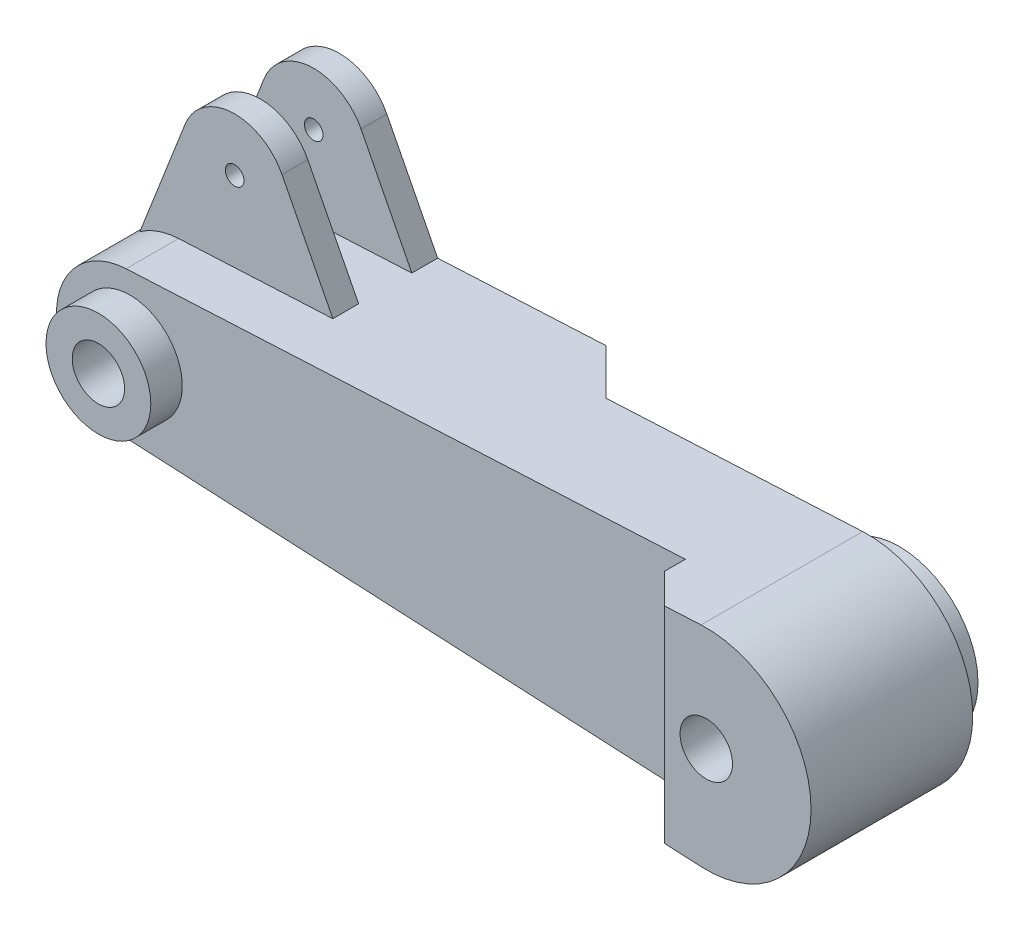
SolidWorks part; units mm, degrees
ref_plane "Front Plane" through (0, 0, 0) normal (0, 0, 1) x (1, 0, 0)
ref_plane "Top Plane" through (0, 0, 0) normal (0, 1, 0) x (1, 0, 0)
ref_plane "Right Plane" through (0, 0, 0) normal (1, 0, 0) x (0, 0, -1)
sketch "Sketch1" plane through (0, 0, 0) normal (0, 0, 1) x (1, 0, 0)
  line L0 (-60.35, 6.9912) -> (-0.5, 9.9875)
  line L1 (-60.35, -6.9912) -> (-0.5, -9.9875)
  arc A0 (-0.5, -9.9875) -> (-0.5, 9.9875) centre (0, 0) ccw
  arc A1 (-60.35, 6.9912) -> (-60.35, -6.9912) centre (-60, 0) ccw
  point P1 (0, 0)
  point P4 (-81.6059, 0)
  dimension "D1" = 7
  dimension "D2" = 10
  dimension "D3" = 60
extrude "Boss-Extrude1" add sketch "Sketch1" along normal blind 20
sketch "Sketch2" plane through (0, 0, 20) normal (0, 0, 1) x (1, 0, 0)
  circle A0 centre (-60, 0) radius 2.5
  arc A1 (-60.35, 6.9912) -> (-60.35, -6.9912) centre (-60, 0) ccw construction
  circle A2 centre (0, 0) radius 2.5
  dimension "D1" = 5
  dimension "D2" = 5
extrude "Cut-Extrude1" cut sketch "Sketch2" against normal through all
sketch "Sketch5" plane through (0, 0, 0) normal (0, 0, 1) x (1, 0, 0)
  line L0 (-60.35, 6.9912) -> (-45.6303, 7.7282)
  line L1 (-0.5, 9.9875) -> (-60.35, 6.9912) construction
  line L2 (-45.6303, 7.7282) -> (-50.4775, 17.2024)
  line L3 (-59.7309, 16.7392) -> (-63.6077, 6.8282)
  line L4 (-63.6077, 6.8282) -> (-64.0436, 5.714)
  arc A0 (-50.4775, 17.2024) -> (-59.7309, 16.7392) centre (-55, 14.8886) ccw
  arc A2 (-60.35, 6.9912) -> (-64.0436, 5.714) centre (-60, 0) ccw
  arc A4 (-60.35, 6.9912) -> (-60.35, -6.9912) centre (-60, 0) ccw construction
  point P10 (-80, 13.9997)
  point P11 (0, 0)
  point P13 (0, 0)
  point P14 (0, 0)
  point P15 (0, 0)
  point P16 (-88.9113, 4.8006)
  point P17 (-74.7989, 3.1519)
  point P18 (-87.0534, -4.0599)
  point P19 (-61.5415, 6.8282)
  point P23 (-69.0127, 13.1089)
  point P24 (-66.8473, -1.4539)
  point P25 (0, 0)
  dimension "D1" = 5.08
  dimension "D2" = 7.62
  dimension "D3" = 18
  dimension "D4" = 5
extrude "Boss-Extrude4" add sketch "Sketch5" along normal blind 10
ref_plane "Plane1" through (-63.5981, -3.1839, 0) normal (0.9987, 0.05, 0) x (0, 0, -1)
sketch "Sketch6" plane through (-63.5981, -3.1839, 0) normal (0.9987, 0.05, 0) x (0, 0, -1)
  line L0 (-10, 10) -> (-20, 10) construction
  line L1 (-7.54, 10) -> (-2.46, 10)
  line L2 (-7.54, 10) -> (-7.54, 27.7)
  line L3 (-7.54, 27.7) -> (-2.46, 27.7)
  line L4 (-2.46, 10) -> (-2.46, 27.7)
  line L5 (0, 22.7) -> (-10, 22.7) construction
  line L6 (-10, 19.7048) -> (0, 19.7048) construction
  point P10 (-5, 19.7048)
  point P11 (-5, 10)
  dimension "D1" = 5.08
  dimension "D2" = 5
extrude "Cut-Extrude2" cut sketch "Sketch6" against normal through all both and the other way through all
sketch "Sketch7" plane through (0, 0, 20) normal (0, 0, 1) x (1, 0, 0)
  circle A0 centre (-55, 14.8886) radius 0.889
  arc A1 (-50.4775, 17.2024) -> (-59.7309, 16.7392) centre (-55, 14.8886) ccw construction
  dimension "D1" = 1.778
extrude "Cut-Extrude3" cut sketch "Sketch7" against normal through all
sketch "Sketch8" plane through (0, 0, 0) normal (0, 1, 0) x (1, 0, 0)
  line L0 (-0.5, 0) -> (-45.6303, 0) construction
  line L1 (-30, 0) -> (10, 0)
  line L2 (-30, 0) -> (-30, -4.572)
  line L3 (-30, -4.572) -> (10, -4.572)
  line L4 (10, 0) -> (10, -4.572)
  line L5 (10, -20) -> (10, 0) construction
  line L6 (-67, 0) -> (-67, -20) construction
  line L7 (-67, -15) -> (-7, -15)
  line L8 (-67, -15) -> (-67, -20)
  line L9 (-67, -20) -> (-7, -20)
  line L10 (-7, -15) -> (-7, -20)
  line L11 (-0.5, -20) -> (-60.35, -20) construction
  dimension "D1" = 4.572
  dimension "D2" = 40
  dimension "D3" = 5
  dimension "D4" = 60
extrude "Cut-Extrude4" cut sketch "Sketch8" against normal through all both and the other way through all
sketch "Sketch4" plane through (0, 0, 4.572) normal (0, 0, -1) x (-1, 0, 0)
  circle A0 centre (0, 0) radius 7.5
  circle A1 centre (0, 0) radius 2.5
  point P4 (0, 0)
  dimension "D1" = 15
  dimension "D2" = 5
extrude "Boss-Extrude3" add sketch "Sketch4" along normal blind 3
chamfer "Chamfer1" distance 5 angle 45 1 edges at (-30, 0, 4.572)
sketch "Sketch3" plane through (0, 0, 15) normal (0, 0, 1) x (1, 0, 0)
  circle A0 centre (-60, 0) radius 5
  circle A1 centre (-60, 0) radius 2.5
  dimension "D1" = 10
  dimension "D2" = 5
extrude "Boss-Extrude2" add sketch "Sketch3" along normal blind 3 contours A0 | A1
chamfer "Chamfer2" distance 3 angle 45 1 edges at (-7, 0, 20)
